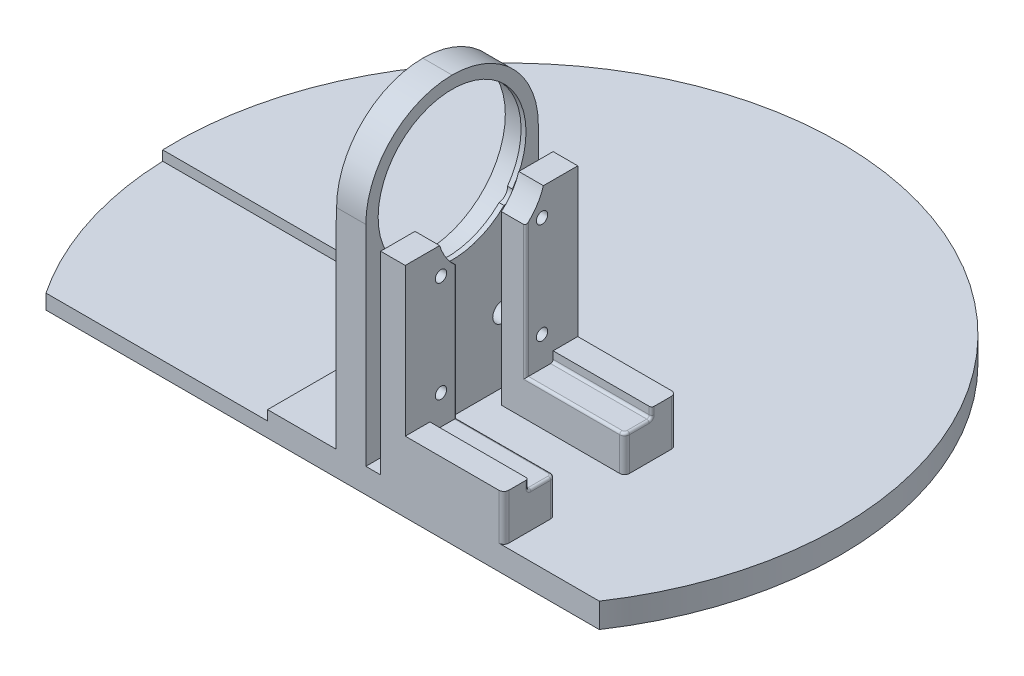
SolidWorks part; units mm, degrees
ref_plane "정면" through (0, 0, 0) normal (0, 0, 1) x (1, 0, 0)
ref_plane "윗면" through (0, 0, 0) normal (0, 1, 0) x (1, 0, 0)
ref_plane "우측면" through (0, 0, 0) normal (1, 0, 0) x (0, 0, -1)
sketch "스케치1" plane through (0, 0, 0) normal (0, 1, 0) x (1, 0, 0)
  circle A0 centre (0, 0) radius 67.5
  dimension "D1" = 135
extrude "보스-돌출1" add sketch "스케치1" along normal blind 5
sketch "스케치2" plane through (0, 5, 0) normal (0, 1, 0) x (1, 0, 0)
  line L1 (2.76, -2.5) -> (8.76, -2.5)
  line L2 (2.76, -2.5) -> (2.76, -37.5)
  line L3 (2.76, -37.5) -> (8.76, -37.5)
  line L4 (8.76, -2.5) -> (8.76, -37.5)
  point P4 (8.76, -20)
  dimension "D1" = 2.76
  dimension "D2" = 6
  dimension "D3" = 35
  dimension "D4" = 20
extrude "보스-돌출2" add sketch "스케치2" along normal blind 60
fillet "필렛1" radius 17.5 2 edges at (5.76, 65, 2.5) (5.76, 65, 37.5)
sketch "스케치3" plane through (2.76, 0, 0) normal (-1, 0, 0) x (0, 0, 1)
  circle A0 centre (20, 47.5) radius 16
  dimension "D1" = 32
extrude "컷-돌출1" cut sketch "스케치3" against normal blind 5
chamfer "모따기1" distance 0.8 angle 64 1 edges at (2.76, 47.5, 36) first distance on face at (7.76, 47.5, 36)
sketch "스케치4" plane through (7.76, 0, 0) normal (-1, 0, 0) x (0, 0, 1)
  circle A0 centre (20, 47.5) radius 15
  circle A1 centre (20, 47.5) radius 16 construction
  dimension "D1" = 1
extrude "컷-돌출2" cut sketch "스케치4" against normal through all
sketch "스케치6" plane through (8.76, 0, 0) normal (1, 0, 0) x (0, 0, -1)
  line L5 (-2.5, 27.5) -> (-2.5, 21.5)
  line L6 (-2.5, 27.5) -> (-4.5, 27.5)
  line L7 (-2.5, 21.5) -> (-4.5, 21.5)
  line L8 (-4.5, 27.5) -> (-4.5, 21.5)
  line L9 (-2.5, 47.5) -> (-2.5, 5) construction
  circle A0 centre (-20, 47.5) radius 15 construction
  dimension "D4" = 20
  dimension "D2" = 2
extrude "컷-돌출3" cut sketch "스케치6" against normal through all
sketch "스케치8" plane through (0, 0, 4.5) normal (0, 0, -1) x (-1, 0, 0)
  line L0 (-2.76, 27.5) -> (-8.76, 27.5) construction
  line L1 (-2.76, 27.5) -> (-2.76, 21.5) construction
  circle A0 centre (-5.76, 24.5) radius 1.6
  dimension "D1" = 3
  dimension "D2" = 3
  dimension "D3" = 3.2
extrude "컷-돌출5" cut sketch "스케치8" against normal blind 6
sketch "스케치9" plane through (0, 0, 4.5) normal (0, 0, -1) x (-1, 0, 0)
  line L0 (-2.76, 21.5) -> (-8.76, 21.5) construction
  line L3 (-4.3166, 27) -> (-7.2034, 27)
  line L4 (-7.2034, 27) -> (-8.6468, 24.5)
  line L5 (-8.6468, 24.5) -> (-7.2034, 22)
  line L6 (-7.2034, 22) -> (-4.3166, 22)
  line L7 (-4.3166, 27) -> (-2.76, 27)
  line L8 (-2.76, 27.5) -> (-2.76, 21.5) construction
  line L9 (-2.76, 27) -> (-2.76, 22)
  line L10 (-2.76, 22) -> (-4.3166, 22)
  line L12 (-2.8732, 24.5) -> (-4.3166, 27) [skipped]
  line L13 (-4.3166, 22) -> (-2.8732, 24.5) [skipped]
  circle A0 centre (-5.76, 24.5) radius 2.5 construction
  dimension "D1" = 5
extrude "컷-돌출8" cut sketch "스케치9" against normal blind 2.2 from offset 2 offset against normal yes
sketch "스케치11" plane through (0, 5, 0) normal (0, 1, 0) x (1, 0, 0)
  line L0 (11.76, -2.5) -> (36.76, -2.5)
  line L1 (11.76, -2.5) -> (11.76, -13)
  line L2 (36.76, -2.5) -> (36.76, -13)
  line L3 (11.76, -13) -> (36.76, -13)
  line L4 (11.76, -27) -> (36.76, -27)
  line L5 (11.76, -27) -> (11.76, -37.5)
  line L6 (36.76, -27) -> (36.76, -37.5)
  line L7 (11.76, -37.5) -> (36.76, -37.5)
  line L8 (8.76, -2.5) -> (2.76, -2.5) construction
  line L9 (8.76, -37.5) -> (8.76, -2.5) construction
  dimension "D1" = 35
  dimension "D2" = 10.5
  dimension "D3" = 3
  dimension "D4" = 25
extrude "보스-돌출4" add sketch "스케치11" along normal blind 7.3
sketch "스케치12" plane through (0, 12.3, 0) normal (0, 1, 0) x (1, 0, 0)
  line L0 (16.76, -32.5) -> (36.76, -32.5)
  line L1 (11.76, -2.5) -> (36.76, -2.5)
  line L2 (11.76, -2.5) -> (11.76, -13)
  line L3 (11.76, -13) -> (16.76, -13)
  line L4 (36.76, -2.5) -> (36.76, -7.5)
  line L5 (11.76, -27) -> (16.76, -27)
  line L6 (11.76, -27) -> (11.76, -37.5)
  line L7 (11.76, -37.5) -> (36.76, -37.5)
  line L8 (36.76, -32.5) -> (36.76, -37.5)
  line L9 (16.76, -7.5) -> (36.76, -7.5)
  line L10 (16.76, -7.5) -> (16.76, -13)
  line L11 (16.76, -27) -> (16.76, -32.5)
  line L12 (11.76, -13) -> (36.76, -13) construction
  line L13 (11.76, -27) -> (36.76, -27) construction
  line L14 (16.76, -2.5) -> (16.76, -13) construction
  line L15 (11.76, -7.5) -> (36.76, -7.5) construction
  line L16 (11.76, -32.5) -> (36.76, -32.5) construction
  line L17 (16.76, -27) -> (16.76, -37.5) construction
  dimension "D1" = 5.5
  dimension "D2" = 5.5
  dimension "D3" = 5
extrude "보스-돌출5" add sketch "스케치12" along normal blind 2
fillet "필렛3" radius 1 4 edges at (36.76, 8.65, 27) (36.76, 8.65, 13) (36.76, 9.65, 2.5) (36.76, 9.65, 37.5)
sketch "스케치13" plane through (16.76, 0, 0) normal (1, 0, 0) x (0, 0, -1)
  line L0 (-27, 14.3) -> (-37.5, 14.3)
  line L1 (-27, 14.3) -> (-27, 39.0147)
  line L2 (-37.5, 14.3) -> (-37.5, 44.3)
  line L3 (-30.5243, 44.3) -> (-37.5, 44.3)
  line L4 (-13, 14.3) -> (-2.5, 14.3)
  line L5 (-13, 14.3) -> (-13, 39.0147)
  line L6 (-2.5, 14.3) -> (-2.5, 44.3)
  line L7 (-9.4757, 44.3) -> (-2.5, 44.3)
  line L10 (-2.5, 21.5) -> (-2.5, 5) construction
  arc A0 (-30.5243, 44.3) -> (-27, 39.0147) centre (-20, 47.5) ccw
  arc A1 (-13, 39.0147) -> (-9.4757, 44.3) centre (-20, 47.5) ccw
  dimension "D2" = 22
  dimension "D1" = 30
extrude "보스-돌출6" add sketch "스케치13" against normal blind 5
sketch "스케치14" plane through (16.76, 0, 0) normal (1, 0, 0) x (0, 0, -1)
  line L1 (-30.25, 38.8) -> (-9.75, 38.8) construction
  line L2 (-30.25, 38.8) -> (-30.25, 18.3) construction
  line L3 (-30.25, 18.3) -> (-9.75, 18.3) construction
  line L4 (-9.75, 38.8) -> (-9.75, 18.3) construction
  line L8 (-32.5, 12.3) -> (-27, 12.3) construction
  circle A1 centre (-20, 47.5) radius 15 construction
  circle A2 centre (-30.25, 18.3) radius 1.15
  circle A3 centre (-9.75, 18.3) radius 1.15
  circle A4 centre (-9.75, 38.8) radius 1.15
  circle A5 centre (-30.25, 38.8) radius 1.15
  dimension "D5" = 2.3
  dimension "D1" = 20.5
  dimension "D2" = 20.5
  dimension "D3" = 6
  dimension "D4" = 10.25
extrude "컷-돌출10" cut sketch "스케치14" against normal through all
fillet "필렛2" radius 0.5 12 edges at (26.76, 12.3, 32.5) (26.76, 12.3, 7.5) (36.76, 13.3, 7.5) (36.76, 13.3, 32.5) (36.76, 12.3, 9.75) (36.76, 12.3, 30.25) (26.26, 12.3, 13) (36.4671, 12.3, 12.7071) (26.26, 12.3, 27) (36.4671, 12.3, 27.2929) (16.76, 25.6574, 13) (16.76, 25.6574, 27)
sketch "스케치15" plane through (2.76, 0, 0) normal (-1, 0, 0) x (0, 0, 1)
  circle A0 centre (9.75, 38.8) radius 2
  circle A1 centre (30.25, 38.8) radius 2
  circle A2 centre (9.75, 18.3) radius 2
  circle A3 centre (30.25, 18.3) radius 2
  dimension "D1" = 4
extrude "컷-돌출11" cut sketch "스케치15" against normal blind 10
sketch "스케치16" plane through (0, 5, 0) normal (0, 1, 0) x (1, 0, 0)
  line L0 (2.8284, -2.5) -> (2.8284, -20) construction
  line L1 (-11.1716, -2.5) -> (-67.5, -2.5)
  line L2 (-11.1716, -2.5) -> (-11.1716, -67.5)
  line L3 (-11.1716, -67.5) -> (-67.5, -67.5)
  line L4 (-67.5, -2.5) -> (-67.5, -67.5)
  line L6 (35.76, -2.5) -> (16.76, -2.5) construction
  circle A0 centre (0, 0) radius 67.5 construction
  dimension "D2" = 14
extrude "컷-돌출12" cut sketch "스케치16" against normal blind 2
sketch "스케치17" plane through (0, 5, 0) normal (0, 1, 0) x (1, 0, 0)
  line L0 (11.76, -37.5) -> (35.76, -37.5) construction
  line L1 (56.1249, -37.5) -> (-56.1249, -37.5)
  line L2 (56.1249, -37.5) -> (56.1249, -67.5)
  line L3 (56.1249, -67.5) -> (-56.1249, -67.5)
  line L4 (-56.1249, -37.5) -> (-56.1249, -67.5)
  arc A0 (-11.1716, -66.5691) -> (-67.4537, -2.5) centre (0, 0) ccw construction
extrude "컷-돌출13" cut sketch "스케치17" against normal through all
